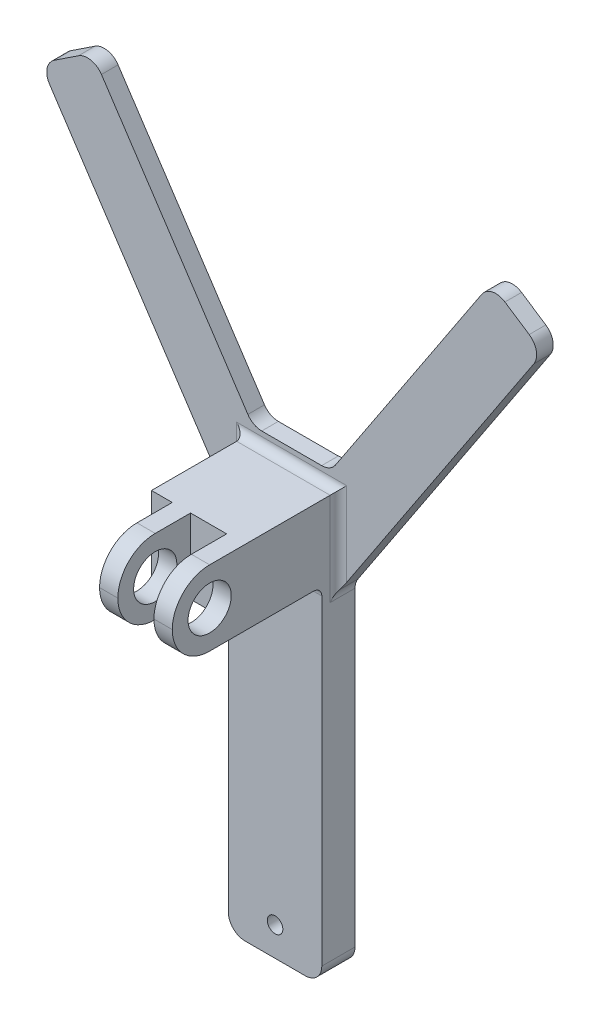
SolidWorks part; units mm, degrees
ref_plane "Plan de face" through (0, 0, 0) normal (0, 0, 1) x (1, 0, 0)
ref_plane "Plan de dessus" through (0, 0, 0) normal (0, 1, 0) x (1, 0, 0)
ref_plane "Plan de droite" through (0, 0, 0) normal (1, 0, 0) x (0, 0, -1)
sketch "Sketch1" plane through (0, 0, 0) normal (0, 0, 1) x (1, 0, 0)
  line L18 (-11.895, 65.5892) -> (11.895, 65.5892)
  line L19 (11.895, 65.5892) -> (60.9587, 139.724)
  line L20 (60.9587, 139.724) -> (76.8447, 129.2103)
  line L21 (76.8447, 129.2103) -> (14.2875, 34.687)
  line L23 (14.2875, 34.687) -> (14.2875, -66.913)
  line L24 (14.2875, -66.913) -> (-14.2875, -66.913)
  line L25 (-14.2875, -66.913) -> (-14.2875, 34.687)
  line L26 (-14.2875, 34.687) -> (-76.8447, 129.2103)
  line L27 (-76.8447, 129.2103) -> (-60.9587, 139.724)
  line L28 (-60.9587, 139.724) -> (-11.895, 65.5892)
  line L29 (-14.2875, 34.687) -> (14.2875, 34.687) construction
  point P2 (0, 34.687)
  point P12 (0, 65.5892)
  point P13 (12.7, 8.9504)
  point P14 (25.4, 30.9071)
  point P16 (16.9538, 31.3694)
  dimension "D1" = 28.575
  dimension "D2" = 19.05
  dimension "D3" = 88.9
  dimension "D4" = 88.9
  dimension "D5" = 101.6
extrude "Boss-Extrude1" add sketch "Sketch1" along normal blind 5.08
sketch "Sketch3" plane through (0, 0, 5.08) normal (0, 0, 1) x (1, 0, 0)
  line L0 (0, 65.5892) -> (0, 34.687) construction
  line L5 (14.2875, 38.7081) -> (-14.2875, 38.7081)
  line L6 (14.2875, 38.7081) -> (14.2875, 61.5681)
  line L7 (14.2875, 61.5681) -> (-14.2875, 61.5681)
  line L8 (-14.2875, 38.7081) -> (-14.2875, 61.5681)
  line L9 (14.2875, 38.7081) -> (-14.2875, 61.5681) construction
  line L10 (14.2875, 61.5681) -> (-14.2875, 38.7081) construction
  line L12 (11.895, 65.5892) -> (-11.895, 65.5892) construction
  point P0 (0, 50.1381)
  point P5 (0, 0)
  point P15 (0, 50.1381)
  dimension "D1" = 28.575
  dimension "D2" = 22.86
extrude "Boss-Extrude2" add sketch "Sketch3" along normal blind 50.8
sketch "Sketch6" plane through (0, 0, 5.08) normal (0, 0, 1) x (1, 0, 0)
  line L6 (-14.2875, 34.687) -> (-14.2875, -66.913) construction
  line L11 (-14.2875, 38.7081) -> (14.2875, 38.7081)
  line L12 (-14.2875, 38.7081) -> (-14.2875, -66.913)
  line L13 (-14.2875, -66.913) -> (14.2875, -66.913)
  line L14 (14.2875, 38.7081) -> (14.2875, -66.913)
  line L15 (-14.2875, -66.913) -> (14.2875, -66.913) construction
  line L16 (14.2875, -66.913) -> (14.2875, 34.687) construction
  line L17 (-14.2875, 38.7081) -> (14.2875, 38.7081) construction
extrude "Boss-Extrude3" add sketch "Sketch6" along normal blind 5.08
fillet "Fillet1" radius 5.08 10 edges at (-14.2875, -66.913, 5.08) (14.2875, -66.913, 5.08) (76.8447, 129.2103, 2.54) (60.9587, 139.724, 2.54) (-60.9587, 139.724, 2.54) (-76.8447, 129.2103, 2.54) (-11.895, 65.5892, 2.54) (11.895, 65.5892, 2.54) (14.2875, 34.687, 2.54) (-14.2875, 34.687, 2.54)
sketch "Sketch4" plane through (0, 38.7081, 0) normal (0, -1, 0) x (1, 0, 0)
  line L0 (-14.2875, 55.88) -> (14.2875, 55.88) construction
  line L1 (-14.2875, 55.88) -> (-7.9375, 55.88)
  line L2 (-14.2875, 55.88) -> (-14.2875, 33.655)
  line L3 (-14.2875, 33.655) -> (-7.9375, 33.655)
  line L4 (-7.9375, 55.88) -> (-7.9375, 33.655)
  line L5 (-2.3495, 55.88) -> (8.6995, 55.88)
  line L6 (-2.3495, 55.88) -> (-2.3495, 33.655)
  line L7 (-2.3495, 33.655) -> (8.6995, 33.655)
  line L8 (8.6995, 55.88) -> (8.6995, 33.655)
  line L9 (14.2875, 55.88) -> (14.2875, 10.16) construction
  dimension "D1" = 5.588
  dimension "D2" = 5.588
  dimension "D3" = 22.225
  dimension "D4" = 22.225
  dimension "D5" = 6.35
extrude "Cut-Extrude1" cut sketch "Sketch4" against normal through all
fillet "Fillet3" radius 11.43 4 edges at (11.4935, 61.5681, 55.88) (-5.1435, 61.5681, 55.88) (11.4935, 38.7081, 55.88) (-5.1435, 38.7081, 55.88)
sketch "Sketch5" plane through (-7.9375, 0, 0) normal (-1, 0, 0) x (0, 0, 1)
  circle A0 centre (44.45, 50.1381) radius 6.604
  dimension "D1" = 13.208
extrude "Cut-Extrude2" cut sketch "Sketch5" against normal through all
fillet "Fillet6" radius 2.54 4 edges at (14.2875, 47.3632, 5.08) (0, 61.5681, 5.08) (-14.2875, 47.3632, 5.08) (0, 38.7081, 10.16)
sketch "Sketch7" plane through (0, 0, 0) normal (0, 0, -1) x (-1, 0, 0)
  line L0 (9.2075, -66.913) -> (-9.2075, -66.913) construction
  line L1 (14.2875, 33.1582) -> (14.2875, -61.833) construction
  circle A0 centre (0, -58.023) radius 4.2333
  point P2 (0, -19.3268)
  dimension "D1" = 8.4667
  dimension "D2" = 8.89
  dimension "D3" = 14.2875
extrude "Cut-Extrude3" cut sketch "Sketch7" against normal blind 5.08
sketch "Sketch8" plane through (0, 0, 5.08) normal (0, 0, -1) x (-1, 0, 0)
  line L0 (14.2875, 33.1582) -> (14.2875, -61.833) construction
  line L2 (9.2075, -66.913) -> (-9.2075, -66.913) construction
  circle A0 centre (0, -58.023) radius 2.3812
  point P2 (0, 0)
  point P3 (0, -17.683)
  point P4 (0, 0)
  point P6 (0, -19.457)
  point P10 (-1.0526, -28.813)
  point P11 (0, 0)
  dimension "D1" = 4.7625
  dimension "D2" = 14.2875
  dimension "D3" = 8.89
extrude "Cut-Extrude4" cut sketch "Sketch8" against normal through all
